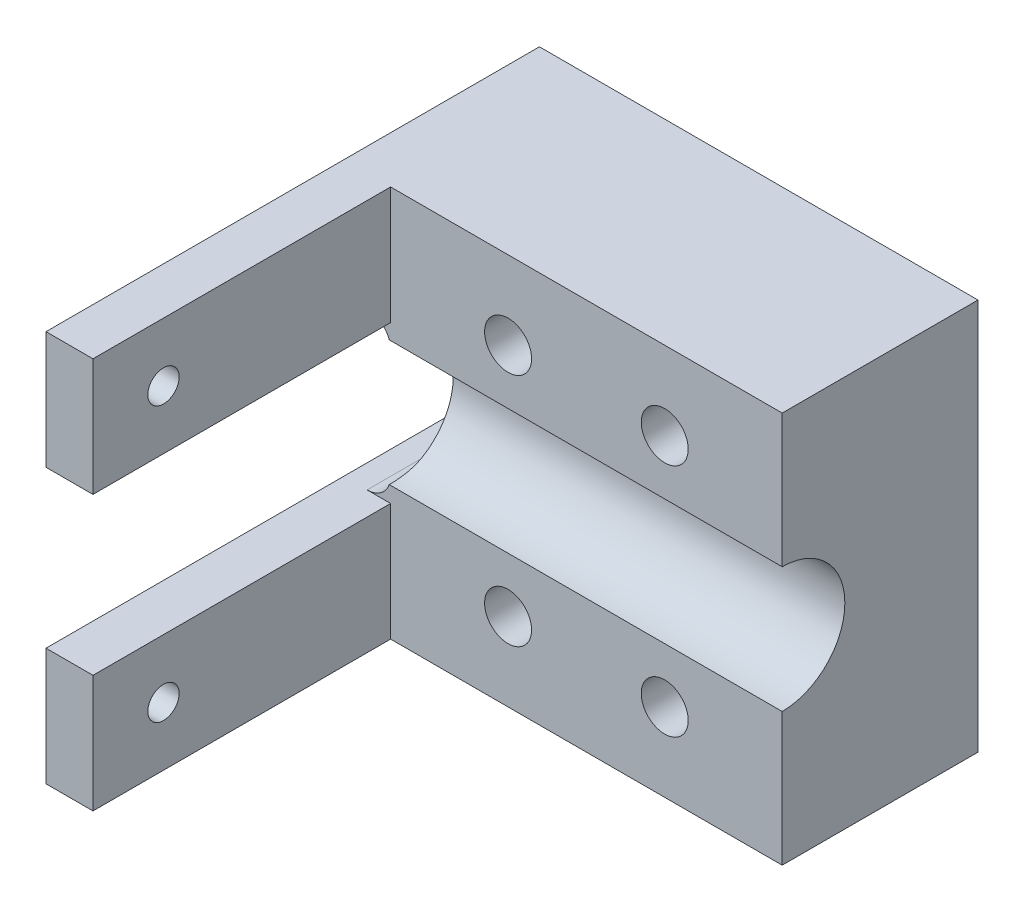
SolidWorks part; units mm, degrees
ref_plane "Front Plane" through (0, 0, 0) normal (0, 0, 1) x (1, 0, 0)
ref_plane "Top Plane" through (0, 0, 0) normal (0, 1, 0) x (1, 0, 0)
ref_plane "Right Plane" through (0, 0, 0) normal (1, 0, 0) x (0, 0, -1)
sketch "Sketch1" plane through (0, 0, 0) normal (0, 0, 1) x (1, 0, 0)
  line L1 (0, 0) -> (50, 0)
  line L2 (0, 0) -> (0, 50)
  line L3 (0, 50) -> (50, 50)
  line L4 (50, 0) -> (50, 50)
  dimension "D1" = 50
  dimension "D2" = 50
extrude "Boss-Extrude1" add sketch "Sketch1" along normal blind 25
sketch "Sketch2" plane through (0, 0, 0) normal (-1, 0, 0) x (0, 0, 1)
  line L0 (25, 50) -> (25, 0) construction
  circle A0 centre (25, 25) radius 8
  dimension "D1" = 16
extrude "Cut-Extrude1" cut sketch "Sketch2" against normal blind 58
sketch "Sketch3" plane through (0, 0, 25) normal (0, 0, 1) x (1, 0, 0)
  line L0 (50, 50) -> (0, 50) construction
  line L1 (50, 33) -> (50, 50) construction
  line L3 (0, 50) -> (0, 33) construction
  line L4 (0, 0) -> (50, 0) construction
  line L5 (0, 17) -> (0, 0) construction
  line L6 (50, 0) -> (50, 17) construction
  circle A0 centre (15, 40) radius 3
  circle A1 centre (35, 40) radius 3
  circle A2 centre (35, 10) radius 3
  circle A3 centre (15, 10) radius 3
  point P18 (0, 8.5)
  dimension "D1" = 10
  dimension "D2" = 10
  dimension "D3" = 15
  dimension "D4" = 15
  dimension "D5" = 6
  dimension "D6" = 6
  dimension "D7" = 6
  dimension "D8" = 6
  dimension "D9" = 10
  dimension "D10" = 10
  dimension "D11" = 15
  dimension "D12" = 15
extrude "Cut-Extrude2" cut sketch "Sketch3" against normal blind 25
sketch "Sketch4" plane through (0, 0, 0) normal (-1, 0, 0) x (0, 0, 1)
  line L0 (0, 50) -> (0, 0) construction
  line L1 (0, 50) -> (63, 50)
  line L2 (0, 50) -> (0, 35)
  line L3 (0, 35) -> (63, 35)
  line L4 (63, 50) -> (63, 35)
  line L5 (25, 50) -> (0, 50) construction
  line L6 (25, 50) -> (25, 33) construction
  line L7 (0, 0) -> (63, 0)
  line L8 (0, 0) -> (0, 15)
  line L9 (0, 15) -> (63, 15)
  line L10 (63, 0) -> (63, 15)
  line L11 (25, 17) -> (25, 0) construction
  dimension "D1" = 38
  dimension "D2" = 38
  dimension "D3" = 15
  dimension "D4" = 15
extrude "Boss-Extrude2" add sketch "Sketch4" along normal blind 6
sketch "Sketch5" plane through (-6, 0, 0) normal (-1, 0, 0) x (0, 0, 1)
  line L0 (0, 0) -> (63, 0) construction
  line L1 (63, 50) -> (0, 50) construction
  line L2 (63, 35) -> (63, 50) construction
  line L3 (63, 0) -> (63, 15) construction
  circle A0 centre (54, 42.5) radius 2
  circle A1 centre (54, 7.5) radius 2
  dimension "D1" = 4
  dimension "D2" = 4
  dimension "D3" = 7.5
  dimension "D4" = 7.5
  dimension "D5" = 9
  dimension "D6" = 9
extrude "Cut-Extrude3" cut sketch "Sketch5" against normal blind 6
chamfer "Chamfer1" distance 2.5 angle 45 2 edges at (-6, 7.5, 56) (-6, 42.5, 56)
fillet "Fillet1" radius 3 2 edges at (0, 15, 12.5) (0, 35, 12.5)
